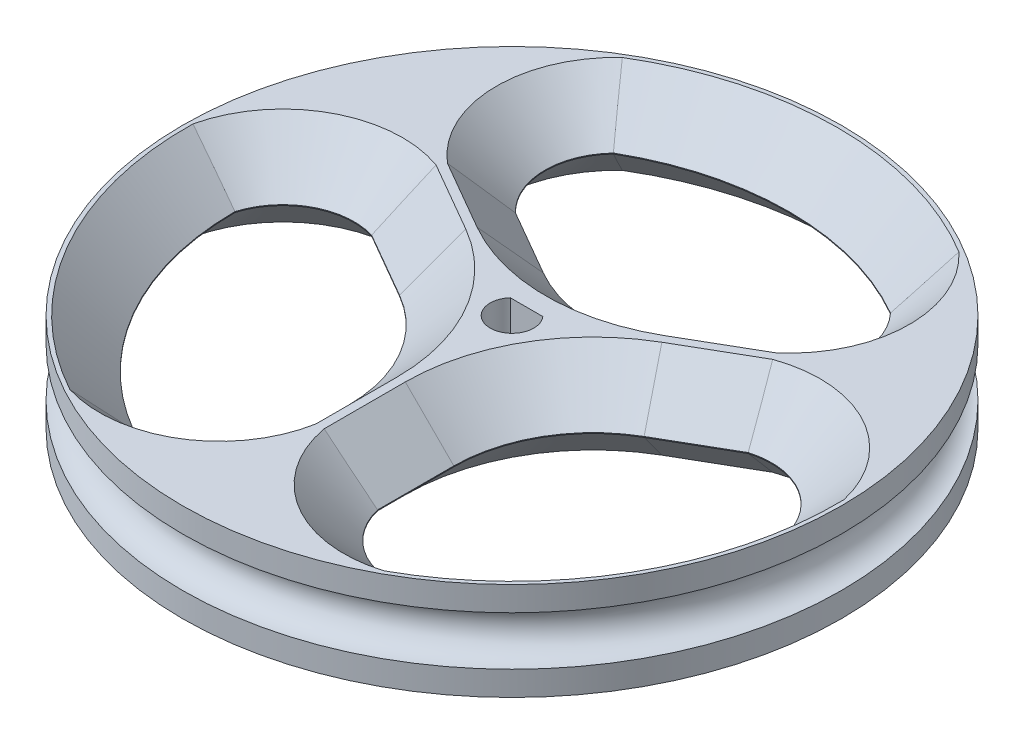
SolidWorks part; units mm, degrees
ref_plane "前视基准面" through (0, 0, 0) normal (0, 0, 1) x (1, 0, 0)
ref_plane "上视基准面" through (0, 0, 0) normal (0, 1, 0) x (1, 0, 0)
ref_plane "右视基准面" through (0, 0, 0) normal (1, 0, 0) x (0, 0, -1)
sketch "Sketch1" plane through (0, 0, 0) normal (0, 1, 0) x (1, 0, 0)
  circle A0 centre (0, 0) radius 23.7871
  dimension "D1" = 47.5742
extrude "Boss-Extrude1" add sketch "Sketch1" along normal blind 7.0612
sketch "Sketch3" plane through (0, 0, 0) normal (1, 0, 0) x (0, 0, -1)
  line L0 (23.7871, 0) -> (23.7871, 7.0612) construction
  circle A0 centre (23.7871, 3.5306) radius 1.7653
  dimension "D1" = 3.5306
revolve "Cut-Revolve1" cut sketch "Sketch3" angle 360 about L0
sketch "Sketch5" plane through (0, 0, 0) normal (0, -1, 0) x (1, 0, 0)
  circle A0 centre (0, 0) radius 1.575
  dimension "D1" = 3.15
extrude "Cut-Extrude1" cut sketch "Sketch5" against normal blind 7.0612
sketch "Sketch8" plane through (0, 0, 0) normal (0, -1, 0) x (1, 0, 0)
  line L0 (1.1739, -1.05) -> (-1.1739, -1.05)
  circle A0 centre (0, 0) radius 1.575 construction
  arc A1 (1.1739, -1.05) -> (-1.1739, -1.05) centre (0, 0) cw
  circle M1 centre (0, 0) radius 1.575
  dimension "D1" = 1.05
extrude "Boss-Extrude3" add sketch "Sketch8" against normal blind 7.0612 contours L0 M1
sketch "Sketch10" plane through (0, 7.0612, 0) normal (0, 1, 0) x (1, 0, 0)
  line L0 (0, 0) -> (0, 29.0992) construction
  line L1 (0, 0) -> (-27.0578, -15.6219) construction
  line L2 (0, 0) -> (29.9058, -17.2661) construction
  line L3 (0, 0) -> (-28.555, 0) construction
  line L4 (0, 0) -> (35.3784, 0) construction
  line L5 (0, 0) -> (0, -30.0819) construction
  line L6 (0, 0) -> (-15.0453, -26.0593) construction
  line L7 (0, 0) -> (14.4632, -25.0509) construction
  line L8 (0, 0) -> (26.4358, 15.2627) construction
  line L9 (0, 0) -> (14.1862, 24.5713) construction
  line L10 (0, 0) -> (-14.8259, 25.6793) construction
  line L11 (0, 0) -> (-27.1804, 15.6926) construction
  line L12 (0, -8) -> (8.1779, -8) construction
  line L13 (-6.9282, 4) -> (-2.7732, 11.1966) construction
  line L14 (6.9282, 4) -> (10.5889, -2.3404) construction
  line L15 (-2.7732, 11.1966) -> (0, 16) construction
  line L16 (0, 16) -> (6.9282, 4) construction
  line L17 (-6.9282, 4) -> (-13.8564, -8) construction
  line L18 (0, -8) -> (-13.8564, -8) construction
  line L19 (8.1779, -8) -> (13.8564, -8) construction
  line L20 (13.8564, -8) -> (10.5889, -2.3404) construction
  line L21 (-3.8, -8) -> (-3.8, -18.0045) construction
  line L22 (3.8, -8) -> (3.8, -20.2776) construction
  line L23 (-8.8282, 0.7091) -> (-19.7526, 7.0163) construction
  line L24 (-5.0282, 7.2909) -> (-16.418, 13.8668) construction
  line L25 (5.0282, 7.2909) -> (12.1691, 11.4137) construction
  line L26 (8.8282, 0.7091) -> (17.5651, 5.7534) construction
  point P27 (-8.8282, 0.7091)
  point P30 (-5.0282, 7.2909)
  point P33 (8.8282, 0.7091)
  point P34 (5.0282, 7.2909)
  dimension "D1" = 120
  dimension "D2" = 120
  dimension "D3" = 30
  dimension "D4" = 30
  dimension "D5" = 30
  dimension "D6" = 30
  dimension "D7" = 30
  dimension "D8" = 8
  dimension "D9" = 8
  dimension "D10" = 8
  dimension "D11" = 0
  dimension "D12" = 180
  dimension "D13" = 0
  dimension "D14" = 3.8
  dimension "D15" = 3.8
  dimension "D16" = 3.8
  dimension "D17" = 3.8
  dimension "D18" = 3.8
  dimension "D19" = 3.8
  dimension "D20" = 3.8
  dimension "D21" = 3.8
  dimension "D22" = 3.8
sketch "Sketch18" plane through (0, 7.0612, 0) normal (0, 1, 0) x (1, 0, 0)
  line L0 (0, 0) -> (-28.555, 0) construction
  line L1 (0, 0) -> (-15.0453, -26.0593) construction
  line L2 (0, 0) -> (14.4632, -25.0509) construction
  line L3 (0, 0) -> (35.3784, 0) construction
  line L4 (0, 0) -> (-14.8259, 25.6793) construction
  line L5 (0, 0) -> (14.1862, 24.5713) construction
  line L6 (0, -8) -> (8.1779, -8) construction
  line L7 (-3.8, -8) -> (-3.8, -18.0045) construction
  line L8 (0, 16) -> (6.9282, 4) construction
  line L9 (-8.8282, 0.7091) -> (-13.5913, 3.4591)
  line L10 (-8.8282, 0.7091) -> (-19.7526, 7.0163) construction
  line L11 (-3.8, -8) -> (-3.8, -13.5)
  line L12 (3.8, -8) -> (3.8, -13.5)
  line L13 (3.8, -8) -> (3.8, -20.2776) construction
  line L14 (8.8282, 0.7091) -> (13.5913, 3.4591)
  line L15 (8.8282, 0.7091) -> (17.5651, 5.7534) construction
  line L16 (5.0282, 7.2909) -> (9.7913, 10.0409)
  line L17 (5.0282, 7.2909) -> (12.1691, 11.4137) construction
  line L18 (-5.0282, 7.2909) -> (-9.7913, 10.0409)
  line L19 (-5.0282, 7.2909) -> (-16.418, 13.8668) construction
  arc A0 (-20, 0) -> (-10, -17.3205) centre (0, 0) ccw
  arc A1 (10, -17.3205) -> (20, 0) centre (0, 0) ccw
  arc A2 (-10, 17.3205) -> (10, 17.3205) centre (0, 0) cw
  arc A3 (8.8282, 0.7091) -> (3.8, -8) centre (13.8564, -8) ccw
  arc A4 (-8.8282, 0.7091) -> (-3.8, -8) centre (-13.8564, -8) cw
  arc A5 (-5.0282, 7.2909) -> (5.0282, 7.2909) centre (0, 16) ccw
  arc A6 (-9.7913, 10.0409) -> (-10, 17.3205) centre (-6.2559, 13.785) cw
  arc A7 (10, 17.3205) -> (9.7913, 10.0409) centre (6.2559, 13.785) cw
  arc A8 (-20, 0) -> (-13.5913, 3.4591) centre (-15.0661, -1.4748) cw
  arc A9 (-10, -17.3205) -> (-3.8, -13.5) centre (-8.8103, -12.3103) ccw
  arc A10 (3.8, -13.5) -> (10, -17.3205) centre (8.8103, -12.3103) ccw
  arc A11 (13.5913, 3.4591) -> (20, 0) centre (15.0661, -1.4748) cw
  dimension "D4" = 5.5
  dimension "D1" = 20
  dimension "D2" = 20
  dimension "D3" = 20
  dimension "D5" = 5.5
  dimension "D6" = 5.5
  dimension "D7" = 5.5
  dimension "D8" = 5.5
  dimension "D9" = 5.5
extrude "Cut-Extrude2" cut sketch "Sketch18" against normal blind 10
chamfer "Chamfer1" distance 3.5 angle 45 6 edges at (-6.1087, 7.0612, 16.6943) (-3.8, 7.0612, 10.75) (-5.1473, 7.0612, 2.9718) (-11.2098, 7.0612, -2.0841) (-17.5121, 7.0612, -3.0568) (-17.3205, 7.0612, 10)
chamfer "Chamfer2" distance 3.5 angle 45 6 edges at (-7.4098, 7.0612, -8.6659) (0, 7.0612, -5.9436) (7.4098, 7.0612, -8.6659) (11.4033, 7.0612, -13.6375) (0, 7.0612, -20) (-11.4033, 7.0612, -13.6375)
chamfer "Chamfer3" distance 3.5 angle 45 6 edges at (6.1087, 7.0612, 16.6943) (17.3205, 7.0612, 10) (17.5121, 7.0612, -3.0568) (11.2098, 7.0612, -2.0841) (5.1473, 7.0612, 2.9718) (3.8, 7.0612, 10.75)
chamfer "Chamfer4" distance 3.5 angle 45 6 edges at (6.1087, 0, 16.6943) (3.8, 0, 10.75) (5.1473, 0, 2.9718) (11.2098, 0, -2.0841) (17.5121, 0, -3.0568) (17.3205, 0, 10)
chamfer "Chamfer5" distance 3.5 angle 45 6 edges at (7.4098, 0, -8.6659) (0, 0, -5.9436) (-7.4098, 0, -8.6659) (-11.4033, 0, -13.6375) (0, 0, -20) (11.4033, 0, -13.6375)
chamfer "Chamfer6" distance 3.5 angle 45 6 edges at (-3.8, 0, 10.75) (-6.1087, 0, 16.6943) (-17.3205, 0, 10) (-17.5121, 0, -3.0568) (-11.2098, 0, -2.0841) (-5.1473, 0, 2.9718)
